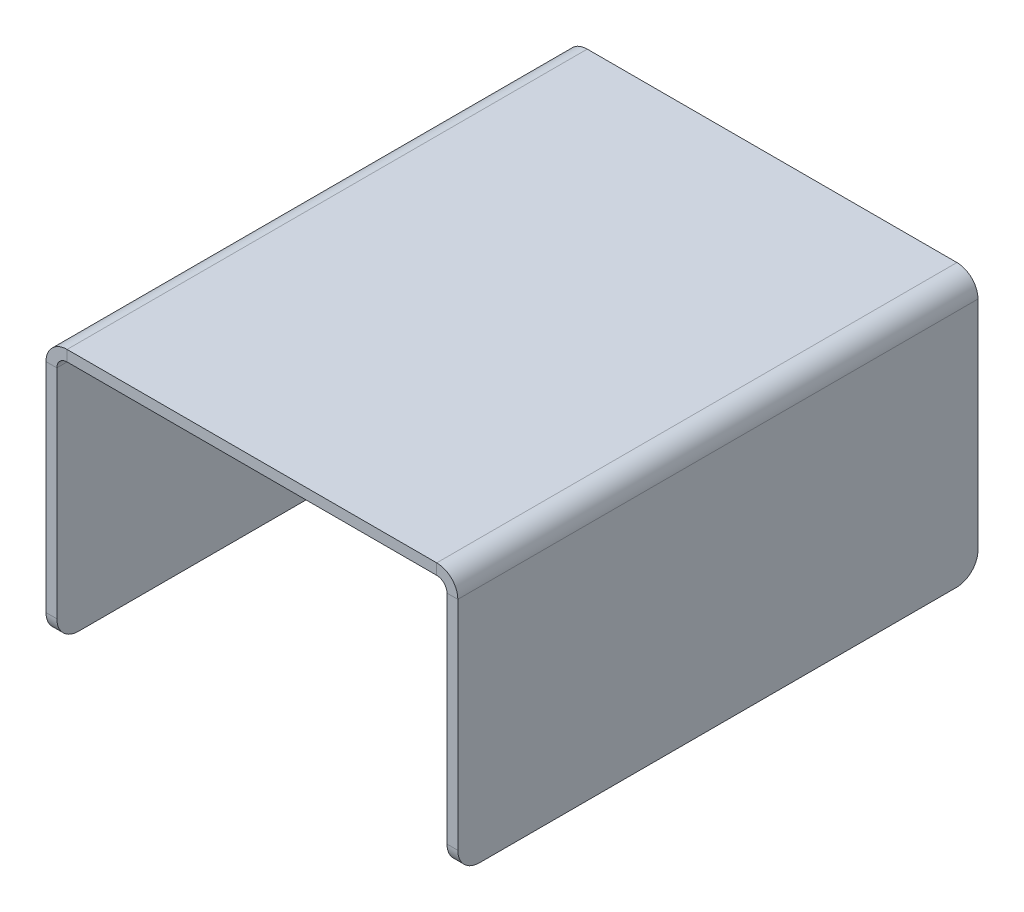
SolidWorks part; units mm, degrees
note: The reader was unsure of these and kept them because the rebuilt part matched: flange length of "Edge-Flange1".
material "6061 Alloy"
ref_plane "Front Plane" through (0, 0, 0) normal (0, 0, 1) x (1, 0, 0)
ref_plane "Top Plane" through (0, 0, 0) normal (0, 1, 0) x (1, 0, 0)
ref_plane "Right Plane" through (0, 0, 0) normal (1, 0, 0) x (0, 0, -1)
sketch "Sketch1" plane through (0, 0, 0) normal (0, 1, 0) x (1, 0, 0)
  line L1 (-57.15, -76.2) -> (57.15, -76.2)
  line L2 (-57.15, -76.2) -> (-57.15, 76.2)
  line L3 (-57.15, 76.2) -> (57.15, 76.2)
  line L4 (57.15, -76.2) -> (57.15, 76.2)
  line L5 (-57.15, -76.2) -> (57.15, 76.2) construction
  line L6 (-57.15, 76.2) -> (57.15, -76.2) construction
  point P0 (0, 0)
  dimension "D1" = 114.3
  dimension "D2" = 152.4
base flange "Base-Flange1" sketch "Sketch1" thickness 3.175 reverse thickness direction no parameters "D1"=3
edge flange "Edge-Flange1" sketch "Sketch10" flange profiles "Sketch10", "Sketch11" flange angle 90 flange length 76.2 flange position material outside bend radius 3 thickness 3.175 relief rectangular parameters "D6"=10, "D8"=1
sketch "Sketch10" plane through (57.15, -3.175, 0) normal (1, 0, 0) x (0, 0, 1)
  line L2 (-76.2, 0) -> (-76.2, 73.025)
  line L3 (-76.2, 73.025) -> (76.2, 73.025)
  line L4 (76.2, 73.025) -> (76.2, 0)
  line L11 (76.2, 0) -> (-76.2, 0) construction
  line L12 (76.2, 0) -> (-76.2, 0)
sketch "Sketch11" plane through (-57.15, -3.175, 0) normal (-1, 0, 0) x (0, 0, -1)
  line L0 (76.2, 0) -> (-76.2, 0) construction
  line L1 (76.2, 0) -> (-76.2, 0)
  line L2 (-76.2, 0) -> (-76.2, 73.025)
  line L3 (-76.2, 73.025) -> (76.2, 73.025)
  line L4 (76.2, 73.025) -> (76.2, 0)
bend "EdgeBend1" bend radius 3 bend angle 90 parameters "D5"=1
bend "EdgeBend2" bend radius 3 bend angle 90 parameters "D5"=2
fillet "Fillet1" radius 6.35 4 edges at (-58.7375, -76.2, 76.2) (-58.7375, -76.2, -76.2) (58.7375, -76.2, 76.2) (58.7375, -76.2, -76.2)
hole_wizard "CSK for #10 Flat Head Machine Screw (100)1" [suppressed] positions "3DSketch1" profile "Sketch12" countersink size "#10" standard "ANSI Inch"
sketch3d "3DSketch1"
  line L0 (-3.175, -3.175, 50.8) -> (-3.175, -3.175, -50.8)
  line L1 (-41.45, -3.175, 50.8) -> (41.45, -3.175, 50.8) construction
  line L2 (41.45, -3.175, -50.8) -> (-41.45, -3.175, -50.8) construction
  line L3 (0, -3.175, 50.8) -> (0, -3.175, -50.8)
  point P0 (-3.175, -3.175, 31.75)
  point P2 (-3.175, -3.175, 0)
  point P4 (-3.175, -3.175, -31.75)
  dimension "D2" = 31.75
  dimension "D1" = 31.75
  dimension "D3" = 3.175
sketch "Sketch12" plane through (-3.175, -3.175, 31.75) normal (1, 0, 0) x (0, 0, -1)
  line L0 (0, 0) -> (0, 3.175)
  line L1 (0, 3.175) -> (2.5527, 3.175)
  line L2 (2.5527, 3.175) -> (2.5527, 1.9608)
  line L3 (2.5527, 1.9608) -> (4.8895, 0)
  line L5 (4.8895, 0) -> (0, 0)
  line L6 (-2.5527, 1.9608) -> (-4.8895, 0) construction
  line L11 (0, -6.35) -> (0, 107.95) construction
  dimension "Thru Hole Dia." = 5.1054
  dimension "Thru Hole Depth" = 3.175
  dimension "Near C'Sink Dia." = 9.779
  dimension "Near C'Sink Angle" = 100
sketch "Bend-Lines1" [suppressed] plane through (0, 0, 0) normal (0, 1, 0) x (1, 0, 0)
sketch "Bounding-Box1" [suppressed] plane through (0, 0, 0) normal (0, 1, 0) x (1, 0, 0)
sheet metal parameters "Sheet-Metal1" thickness 3.175 parameters "D1"=3
flat pattern "Flat-Pattern1" [suppressed]
sketch "Bend-Lines2" plane through (0, 0, 0) normal (0, 1, 0) x (1, 0, 0)
sketch3d "Bounding-Box2" [suppressed]
  line L0 (-50.8, 50.8, 0) -> (50.8, 50.8, 0) construction
  line L1 (-50.8, -50.8, 0) -> (50.8, -50.8, 0) construction
  line L2 (-50.8, 50.8, 0) -> (-50.8, -50.8, 0) construction
  line L3 (50.8, 50.8, 0) -> (50.8, -50.8, 0) construction
sheet metal parameters "Sheet-Metal2" thickness 3.175 parameters "D1"=3
flat pattern "Flat-Pattern1"
sketch "Bend-Lines2" plane through (0, 0, 0) normal (0, 1, 0) x (1, 0, 0)
  line L0 (-57.379, 76.2) -> (-57.379, -76.2) construction
  line L1 (57.379, -76.2) -> (57.379, 76.2) construction
  line L2 (-57.379, 76.2) -> (-57.379, -76.2) construction
  line L3 (57.379, -76.2) -> (57.379, 76.2) construction
sketch3d "Bounding-Box2" [suppressed]
  line L0 (-130.6329, 76.1999, 0) -> (130.6329, 76.2, 0) construction
  line L1 (-130.6329, -76.2, 0) -> (130.633, -76.1999, 0) construction
  line L2 (-130.6329, 76.1999, 0) -> (-130.6329, -76.2, 0) construction
  line L3 (130.6329, 76.2, 0) -> (130.633, -76.1999, 0) construction
bend of the flat pattern "Flatten-<EdgeBend1>1"
bend of the flat pattern "Flatten-<EdgeBend2>1"
sheet metal parameters "Sheet-Metal3" thickness 3.175 parameters "D1"=3
flat pattern "Flat-Pattern1"
sketch "Bend-Lines2" plane through (0, 0, 0) normal (0, 1, 0) x (1, 0, 0)
  line L0 (-44.679, 50.8) -> (-44.679, -50.8) construction
  line L1 (44.679, -50.8) -> (44.679, 50.8) construction
  line L2 (-44.679, 50.8) -> (-44.679, -50.8) construction
  line L3 (44.679, -50.8) -> (44.679, 50.8) construction
sketch3d "Bounding-Box2" [suppressed]
  line L0 (-94.5649, 50.8, 0) -> (94.5649, 50.8, 0) construction
  line L1 (-94.5649, -50.8, 0) -> (94.565, -50.8, 0) construction
  line L2 (-94.5649, 50.8, 0) -> (-94.5649, -50.8, 0) construction
  line L3 (94.5649, 50.8, 0) -> (94.565, -50.8, 0) construction
bend of the flat pattern "Flatten-<EdgeBend1>1"
bend of the flat pattern "Flatten-<EdgeBend2>1"
equation "\"D2@3DSketch1\"=\"D1@3DSketch1\""
